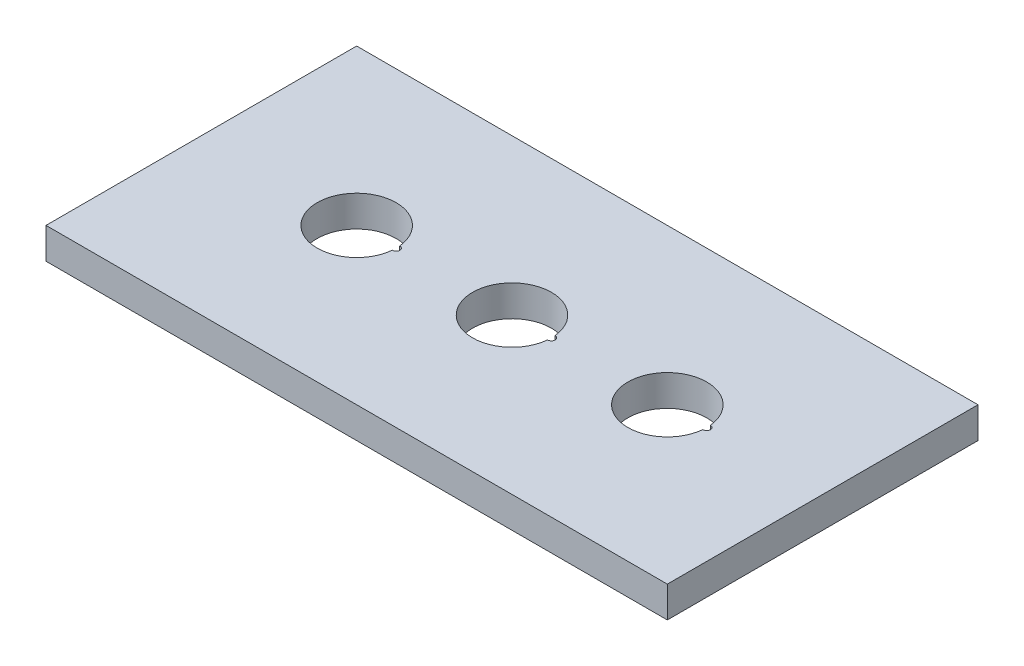
SolidWorks part; units mm, degrees
ref_plane "Front Plane" through (0, 0, 0) normal (0, 0, 1) x (1, 0, 0)
ref_plane "Top Plane" through (0, 0, 0) normal (0, 1, 0) x (1, 0, 0)
ref_plane "Right Plane" through (0, 0, 0) normal (1, 0, 0) x (0, 0, -1)
sketch "Sketch1" plane through (0, 0, 0) normal (0, 1, 0) x (1, 0, 0)
  line L1 (-50, 25) -> (50, 25)
  line L2 (-50, 25) -> (-50, -25)
  line L3 (-50, -25) -> (50, -25)
  line L4 (50, 25) -> (50, -25)
  circle A0 centre (25, 0) radius 6.35 construction
  arc A1 (31.3217, 0.5993) -> (31.3217, -0.5993) centre (31.35, 0) cw
  arc A2 (31.3217, 0.5993) -> (31.3217, -0.5993) centre (25, 0) ccw
  arc A3 (6.3217, 0.5993) -> (6.3217, -0.5993) centre (6.35, 0) cw
  arc A4 (6.3217, 0.5993) -> (6.3217, -0.5993) centre (0, 0) ccw
  arc A5 (-18.6783, 0.5993) -> (-18.6783, -0.5993) centre (-18.65, 0) cw
  arc A6 (-18.6783, 0.5993) -> (-18.6783, -0.5993) centre (-25, 0) ccw
  point P4 (0, 25)
  point P6 (50, 0)
  dimension "D3" = 12.7
  dimension "D4" = 0.6
  dimension "D1" = 100
  dimension "D2" = 50
  dimension "D6" = 25
  dimension "D5" = 3
extrude "Boss-Extrude1" add sketch "Sketch1" along normal blind 5
